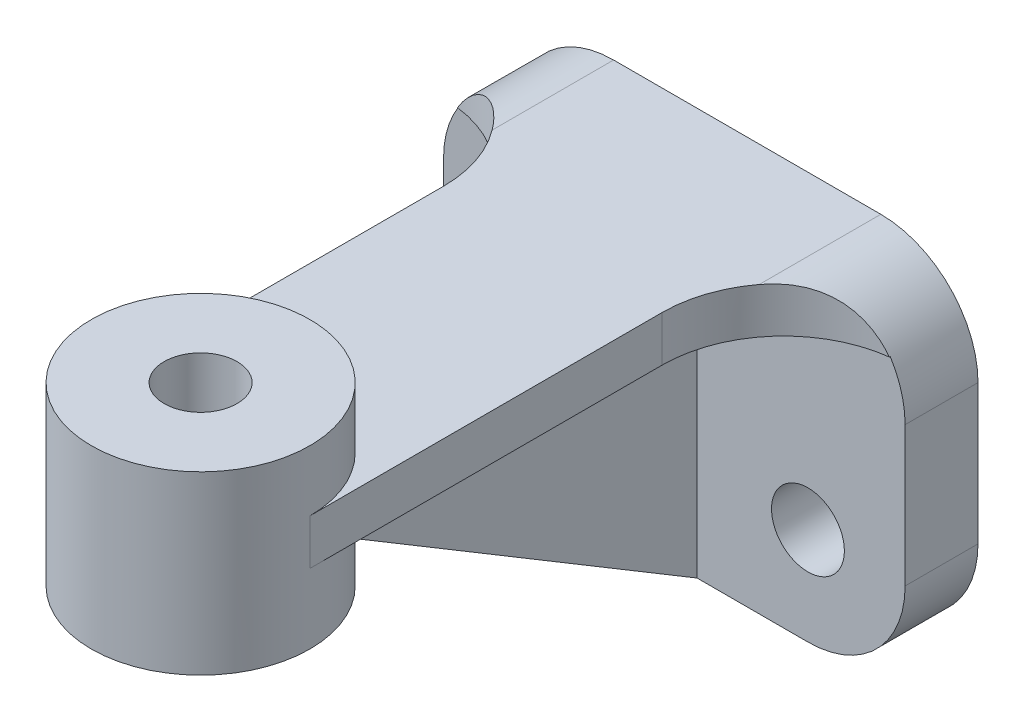
SolidWorks part; units mm, degrees
ref_plane "Front Plane" through (0, 0, 0) normal (0, 0, 1) x (1, 0, 0)
ref_plane "Top Plane" through (0, 0, 0) normal (0, 1, 0) x (1, 0, 0)
ref_plane "Right Plane" through (0, 0, 0) normal (1, 0, 0) x (0, 0, -1)
sketch "Sketch2" plane through (0, 0, 0) normal (0, 1, 0) x (1, 0, 0)
  line L1 (-38, -6) -> (38, -6)
  line L2 (-38, -6) -> (-38, 6)
  line L3 (-38, 6) -> (38, 6)
  line L4 (38, -6) -> (38, 6)
  line L5 (-38, -6) -> (38, 6) construction
  line L6 (-38, 6) -> (38, -6) construction
  line L7 (-18, -6) -> (18, -6)
  line L8 (-18, -6) -> (-18, -84)
  line L9 (-18, -84) -> (18, -84)
  line L10 (18, -6) -> (18, -84)
  circle A0 centre (0, -84) radius 18
  circle A1 centre (0, -84) radius 6
  point P0 (0, 0)
  point P10 (0, -84)
  dimension "D1" = 36
  dimension "D2" = 12
  dimension "D3" = 76
  dimension "D4" = 12
  dimension "D5" = 78
extrude "Boss-Extrude1" add sketch "Sketch2" against normal blind 55 contours L1 L4 L3 L2 region at (0, 0, 0)
extrude "Boss-Extrude2" add sketch "Sketch2<3>" against normal blind 7.5 contours A0 L10 L1 L8 region at (0, 0, 38.0578)
sketch "Sketch2<3>" plane through (0, 0, 0) normal (0, 1, 0) x (1, 0, 0) same geometry as "Sketch2"
extrude "Boss-Extrude3" add sketch "Sketch2<4>" along normal blind 10 and the other way blind 19 contours A1 L9 A0 | A1 L9 A0 region at (0, 0, 75.7239) region at (0, 0, 92.2761)
sketch "Sketch2<4>" plane through (0, 0, 0) normal (0, 1, 0) x (1, 0, 0) same geometry as "Sketch2"
fillet "Fillet1" radius 16 4 edges at (38, -55, 0) (38, 0, 0) (-38, -55, 0) (-38, 0, 0)
hole_wizard "Ø12.0mm Dowel Hole1" positions "Sketch3" profile "Sketch4" hole size "Ø12.0" standard "ANSI Metric" end condition through all
sketch "Sketch3" plane through (0, 0, 6) normal (0, 0, 1) x (1, 0, 0)
  point P0 (-22, -39)
  point P3 (22, -39)
sketch "Sketch4" plane through (-22, -39, 6) normal (1, 0, 0) x (0, -1, 0)
  line L0 (0, 0) -> (0, 12)
  line L1 (0, 12) -> (6, 12)
  line L2 (6, 12) -> (6, 0)
  line L5 (6, 0) -> (0, 0)
  line L11 (0, -6.35) -> (0, 107.95) construction
  dimension "Thru Hole Dia." = 12
  dimension "Thru Hole Depth" = 12
ref_plane "Plane1" through (0, 0, 0) normal (-1, 0, 0) x (0, 0, 1)
sketch "Sketch5" plane through (0, 0, 0) normal (-1, 0, 0) x (0, 0, 1)
  line L0 (66, -19) -> (6, -55)
rib "Rib1" sketch "Sketch5" sketch "Sketch5" thickness 7.5 extrusion direction parallel to sketch draft on no parameters "D1"=7.5
fillet "Fillet2" radius 20 2 edges at (18, -3.75, 6) (-18, -3.75, 6)
